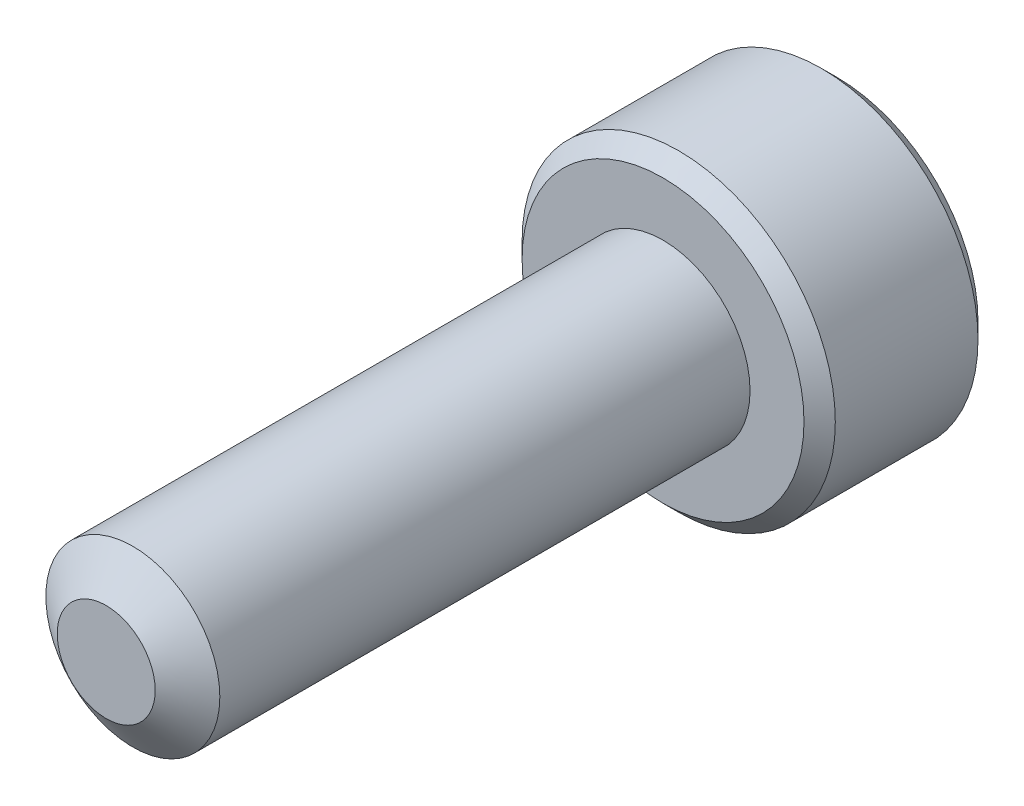
SolidWorks part; units mm, degrees
other "DetailItem1"
ref_plane "Front Plane" through (0, 0, 0) normal (0, 0, 1) x (1, 0, 0)
ref_plane "Top Plane" through (0, 0, 0) normal (0, 1, 0) x (1, 0, 0)
ref_plane "Right Plane" through (0, 0, 0) normal (1, 0, 0) x (0, 0, -1)
sketch "Sketch1" plane through (0, 0, 0) normal (0, 0, 1) x (1, 0, 0)
  circle A0 centre (0, 0) radius 1.25
  dimension "OD" = 2.5
extrude "Extrude1" add sketch "Sketch1" against normal blind 8
sketch "Sketch2" plane through (0, 0, 0) normal (0, 0, 1) x (1, 0, 0)
  circle A0 centre (0, 0) radius 1.25 construction
  circle A1 centre (0, 0) radius 1.25
curve "Helix/Spiral1" pitch 0.45 height 8.45 turns 18.7778 parameters "pitch"=0.45
sketch "Sketch3" plane through (0, 0, 0) normal (1, 0, 0) x (0, 0, -1)
  line L0 (-0.3938, 1.25) -> (-0.225, 0.9577)
  line L1 (-0.225, 0.9577) -> (-0.1688, 0.9577)
  line L2 (-0.1688, 0.9577) -> (0, 1.25)
  line L3 (-0.3938, 1.25) -> (0, 1.25)
  line L4 (-0.1969, 1.25) -> (-0.1969, 0.9577) construction
  line L5 (-0.3094, 1.1039) -> (-0.0844, 1.1039) construction
  line L6 (0, 1.25) -> (0, -1.25) construction
  dimension "D1" = 0.0563
  dimension "D2" = 0.225
  dimension "D3" = 60
sweep "Cut-Sweep1" [suppressed] cut profiles "Sketch3" path "Helix/Spiral1"
sketch "Sketch4" plane through (0, 0, 0) normal (1, 0, 0) x (0, 0, -1)
  line L0 (0.3825, 1.25) -> (0, 0.7037)
  line L1 (0, 0.7037) -> (0, 1.25)
  line L2 (0.3825, 1.25) -> (0, 1.25)
  line L3 (-0.3938, 1.25) -> (0, 1.25) construction
  line L4 (0, 0) -> (7.0209, 0) construction
  dimension "D1" = 55
  dimension "D2" = 0.254
revolve "Cut-Revolve1" cut sketch "Sketch4" angle 360 about L4
sketch "Sketch6" plane through (0, 0, -8) normal (0, 0, -1) x (-1, 0, 0)
  circle A0 centre (0, 0) radius 2.25
  dimension "head dia" = 4.5
extrude "Extrude2" add sketch "Sketch6" along normal blind 2.5
sketch "Sketch7" plane through (0, 0, -10.5) normal (0, 0, -1) x (-1, 0, 0)
  line L1 (0, 1.1547) -> (-1, 0.5774)
  line L2 (-1, 0.5774) -> (-1, -0.5774)
  line L3 (-1, -0.5774) -> (0, -1.1547)
  line L4 (0, -1.1547) -> (1, -0.5774)
  line L5 (1, -0.5774) -> (1, 0.5774)
  line L6 (1, 0.5774) -> (0, 1.1547)
  circle A0 centre (0, 0) radius 1 construction
  dimension "hex dia" = 2
extrude "Cut-Extrude1" cut sketch "Sketch7" against normal blind 1.5
sketch "Sketch8" plane through (0, 0, -10.5) normal (0, 0, -1) x (-1, 0, 0)
  circle A0 centre (0, 0) radius 1.1547
extrude "Cut-Extrude2" cut sketch "Sketch8" against normal through all draft 45
chamfer "Chamfer1" distance 0.225 angle 45 2 edges at (-2.25, 0, -10.5) (-2.25, 0, -8)
sketch "Sketch10" plane through (0, 0, -8) normal (0, 0, 1) x (1, 0, 0)
  circle A1 centre (0, 0) radius 1.25
  circle A2 centre (0, 0) radius 1.25
  dimension "D1" = 0
ref_plane "Plane1" through (0, 0, 0) normal (0, 0, 1) x (1, 0, 0)
extrude "partial thread" [suppressed] add sketch "Sketch10" along normal up to surface (36 mm away) separate body up to plane "Plane1"
chamfer "Chamfer2" [suppressed] distance 0.05 angle 45
combine bodies "Combine1" [suppressed] operation type add bodies to combine 107 108
sketch "Sketch9" plane through (0, 0, 0) normal (1, 0, 0) x (0, 0, -1)
  line L0 (0, 1.25) -> (0, -1.25) construction
  line L1 (1.125, 1.25) -> (1.125, -1.25) construction
  dimension "D1" = 1.125
equation "\"D3@Helix/Spiral1\" = \"screw length@Extrude1\"+\"pitch@Helix/Spiral1\""
equation "\"D1@Sketch3\" = \"pitch@Helix/Spiral1\"*.125"
equation "\"D2@Sketch3\" = \"pitch@Helix/Spiral1\"*.5"
equation "\"D1@Cut-Extrude1\" = \"hex dia@Sketch7\"*.75"
equation "\"D1@Chamfer1\" = \"head dia@Sketch6\"*.05"
equation "\"D1@Sketch9\" = \"pitch@Helix/Spiral1\"*2.5"
equation "\"D1@Chamfer2\"=\"OD@Sketch1\"*.02"
